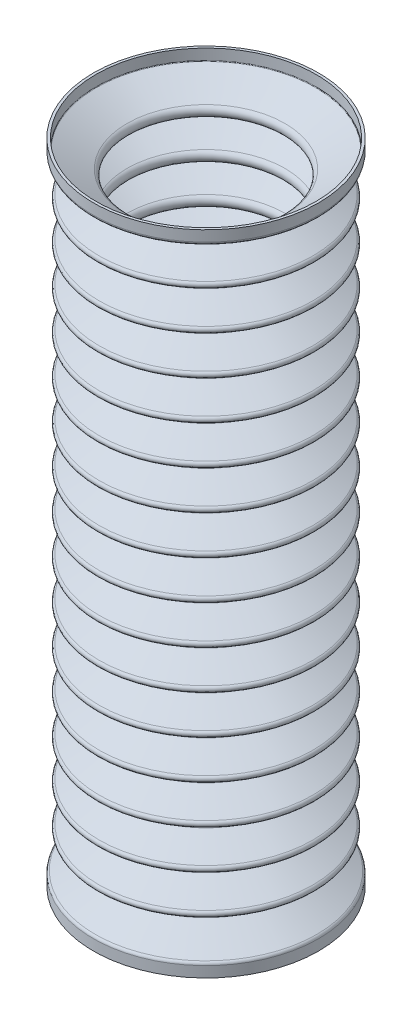
SolidWorks part; units mm, degrees
ref_plane "Front Plane" through (0, 0, 0) normal (0, 0, 1) x (1, 0, 0)
ref_plane "Top Plane" through (0, 0, 0) normal (0, 1, 0) x (1, 0, 0)
ref_plane "Right Plane" through (0, 0, 0) normal (1, 0, 0) x (0, 0, -1)
sketch "Sketch1" plane through (0, 0, 0) normal (0, 0, 1) x (1, 0, 0)
  line L0 (0, 0) -> (0, 304.8)
  line L1 (0, 0) -> (52.959, 0)
  line L2 (52.959, 0) -> (52.959, 5.0364)
  line L3 (35.052, 0) -> (35.052, 304.8) construction
  line L4 (52.1286, 6.3934) -> (37.7072, 13.7639)
  line L5 (37.7072, 16.478) -> (50.3038, 22.9158)
  line L6 (35.052, 15.1209) -> (52.959, 15.1209) construction
  line L7 (52.959, 5.969) -> (52.959, 24.2729) construction
  line L8 (50.3038, 25.6299) -> (37.7072, 32.0678)
  line L9 (37.7072, 34.7819) -> (50.3038, 41.2197)
  line L10 (50.3038, 43.9338) -> (37.7072, 50.3716)
  line L11 (37.7072, 53.0857) -> (50.3038, 59.5236)
  line L12 (50.3038, 62.2377) -> (37.7072, 68.6755)
  line L13 (37.7072, 71.3896) -> (50.3038, 77.8275)
  line L14 (50.3038, 80.5415) -> (37.7072, 86.9794)
  line L15 (37.7072, 89.6935) -> (50.3038, 96.1313)
  line L16 (50.3038, 98.8454) -> (37.7072, 105.2833)
  line L17 (37.7072, 107.9974) -> (50.3038, 114.4352)
  line L18 (50.3038, 117.1493) -> (37.7072, 123.5871)
  line L19 (37.7072, 126.3012) -> (50.3038, 132.7391)
  line L20 (50.3038, 135.4532) -> (37.7072, 141.891)
  line L21 (37.7072, 144.6051) -> (50.3038, 151.043)
  line L22 (50.3038, 153.757) -> (37.7072, 160.1949)
  line L23 (37.7072, 162.909) -> (50.3038, 169.3468)
  line L24 (50.3038, 172.0609) -> (37.7072, 178.4988)
  line L25 (37.7072, 181.2129) -> (50.3038, 187.6507)
  line L26 (50.3038, 190.3648) -> (37.7072, 196.8026)
  line L27 (37.7072, 199.5167) -> (50.3038, 205.9546)
  line L28 (50.3038, 208.6687) -> (37.7072, 215.1065)
  line L29 (37.7072, 217.8206) -> (50.3038, 224.2585)
  line L30 (50.3038, 226.9725) -> (37.7072, 233.4104)
  line L31 (37.7072, 236.1245) -> (50.3038, 242.5623)
  line L32 (50.3038, 245.2764) -> (37.7072, 251.7143)
  line L33 (37.7072, 254.4284) -> (50.3038, 260.8662)
  line L34 (50.3038, 263.5803) -> (37.7072, 270.0181)
  line L35 (37.7072, 272.7322) -> (50.3038, 279.1701)
  line L36 (50.3038, 281.8842) -> (37.7072, 288.322)
  line L37 (37.7072, 291.0361) -> (52.1286, 298.4066)
  line L38 (0, 152.4) -> (155.8281, 152.4) construction
  line L39 (52.959, 304.8) -> (52.959, 299.7636)
  line L40 (0, 304.8) -> (52.959, 304.8)
  arc A0 (52.959, 5.0364) -> (52.1286, 6.3934) centre (51.435, 5.0364) ccw
  arc A1 (52.959, 299.7636) -> (52.1286, 298.4066) centre (51.435, 299.7636) cw
  arc A2 (37.7072, 288.322) -> (37.7072, 291.0361) centre (38.4008, 289.6791) cw
  arc A3 (50.3038, 279.1701) -> (50.3038, 281.8842) centre (49.6102, 280.5271) ccw
  arc A4 (37.7072, 270.0181) -> (37.7072, 272.7322) centre (38.4008, 271.3752) cw
  arc A5 (50.3038, 260.8662) -> (50.3038, 263.5803) centre (49.6102, 262.2232) ccw
  arc A6 (37.7072, 251.7143) -> (37.7072, 254.4284) centre (38.4008, 253.0713) cw
  arc A7 (50.3038, 242.5623) -> (50.3038, 245.2764) centre (49.6102, 243.9194) ccw
  arc A8 (37.7072, 233.4104) -> (37.7072, 236.1245) centre (38.4008, 234.7674) cw
  arc A9 (50.3038, 224.2585) -> (50.3038, 226.9725) centre (49.6102, 225.6155) ccw
  arc A10 (37.7072, 215.1065) -> (37.7072, 217.8206) centre (38.4008, 216.4636) cw
  arc A11 (50.3038, 205.9546) -> (50.3038, 208.6687) centre (49.6102, 207.3116) ccw
  arc A12 (37.7072, 196.8026) -> (37.7072, 199.5167) centre (38.4008, 198.1597) cw
  arc A13 (50.3038, 187.6507) -> (50.3038, 190.3648) centre (49.6102, 189.0077) ccw
  arc A14 (37.7072, 178.4988) -> (37.7072, 181.2129) centre (38.4008, 179.8558) cw
  arc A15 (50.3038, 169.3468) -> (50.3038, 172.0609) centre (49.6102, 170.7039) ccw
  arc A16 (37.7072, 160.1949) -> (37.7072, 162.909) centre (38.4008, 161.5519) cw
  arc A17 (50.3038, 151.043) -> (50.3038, 153.757) centre (49.6102, 152.4) ccw
  arc A18 (37.7072, 141.891) -> (37.7072, 144.6051) centre (38.4008, 143.2481) cw
  arc A19 (50.3038, 132.7391) -> (50.3038, 135.4532) centre (49.6102, 134.0961) ccw
  arc A20 (37.7072, 123.5871) -> (37.7072, 126.3012) centre (38.4008, 124.9442) cw
  arc A21 (50.3038, 114.4352) -> (50.3038, 117.1493) centre (49.6102, 115.7922) ccw
  arc A22 (37.7072, 105.2833) -> (37.7072, 107.9974) centre (38.4008, 106.6403) cw
  arc A23 (50.3038, 96.1313) -> (50.3038, 98.8454) centre (49.6102, 97.4884) ccw
  arc A24 (37.7072, 86.9794) -> (37.7072, 89.6935) centre (38.4008, 88.3364) cw
  arc A25 (50.3038, 77.8275) -> (50.3038, 80.5415) centre (49.6102, 79.1845) ccw
  arc A26 (37.7072, 68.6755) -> (37.7072, 71.3896) centre (38.4008, 70.0326) cw
  arc A27 (50.3038, 59.5236) -> (50.3038, 62.2377) centre (49.6102, 60.8806) ccw
  arc A28 (37.7072, 50.3716) -> (37.7072, 53.0857) centre (38.4008, 51.7287) cw
  arc A29 (50.3038, 41.2197) -> (50.3038, 43.9338) centre (49.6102, 42.5767) ccw
  arc A30 (37.7072, 32.0678) -> (37.7072, 34.7819) centre (38.4008, 33.4248) cw
  arc A31 (50.3038, 22.9158) -> (50.3038, 25.6299) centre (49.6102, 24.2729) ccw
  arc A32 (37.7072, 13.7639) -> (37.7072, 16.478) centre (38.4008, 15.1209) cw
  point P12 (52.959, 15.1209)
  point P37 (52.959, 298.831)
  dimension "D7" = 1.524
  dimension "D1" = 52.959
  dimension "D2" = 5.969
  dimension "D3" = 304.8
  dimension "D4" = 35.052
  dimension "D6" = 18.3039
  dimension "D5" = 16
revolve "Revolve2" add sketch "Sketch1" angle 360 about L0
shell "Shell1" thickness 1.1938 removed face at (52.959, 0, 0) removed face at (52.959, 304.8, 0)
ref_axis "Axis1" through (0, 316.992, 0) along (0, -1, 0)
